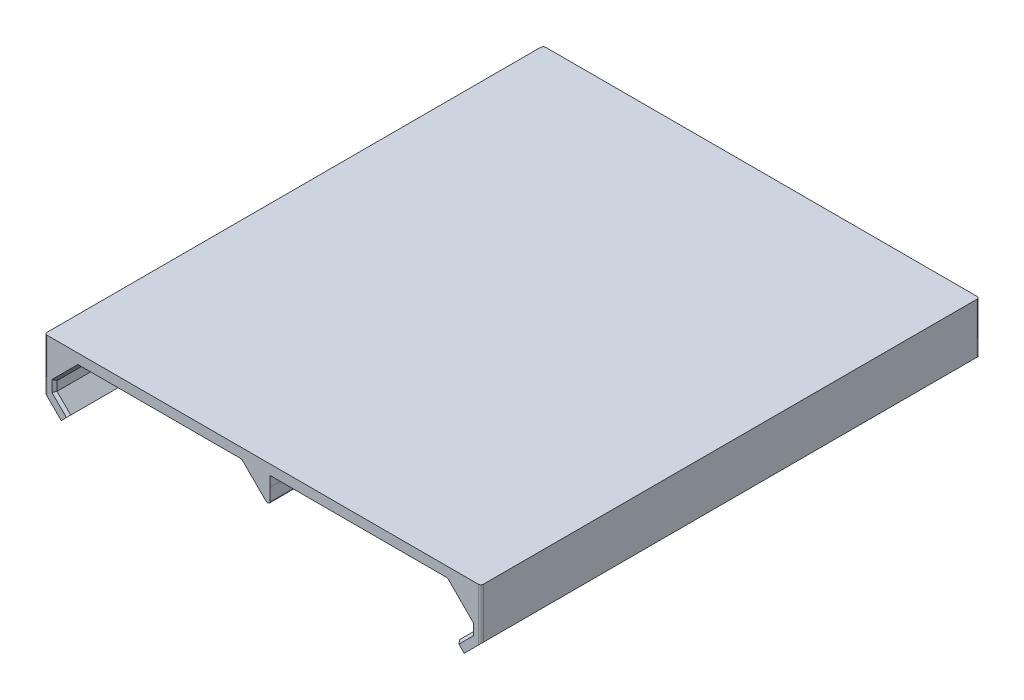
SolidWorks part; units mm, degrees
ref_plane "前视基准面" through (0, 0, 0) normal (0, 0, 1) x (1, 0, 0)
ref_plane "上视基准面" through (0, 0, 0) normal (0, 1, 0) x (1, 0, 0)
ref_plane "右视基准面" through (0, 0, 0) normal (1, 0, 0) x (0, 0, -1)
other "Configuration Table"
sketch "草图1" plane through (0, 0, 0) normal (0, 0, 1) x (1, 0, 0)
  line L0 (0, 0) -> (0, 52) construction
  line L1 (72.7071, 52) -> (-72.7071, 52)
  line L2 (-72.7071, 52) -> (-83.5, 41.2071)
  line L3 (-83.5, 41.2071) -> (-83.5, 37.5)
  line L4 (-83.5, 37.5) -> (-78, 32)
  line L5 (-83, 37) -> (-77, 31) construction
  line L6 (-77, 47) -> (-83, 41) construction
  line L7 (-83, 41) -> (-83, 37) construction
  line L8 (77, 47) -> (74, 47) construction
  line L9 (-77, 31) -> (-77, 0) construction
  line L10 (83.5, 37.5) -> (78, 32)
  line L11 (83.5, 41.2071) -> (83.5, 37.5)
  line L12 (72.7071, 52) -> (83.5, 41.2071)
  line L15 (3.0155, 52) -> (3, 52)
  dimension "D1" = 0.5
  dimension "D2" = 0.5
  dimension "D3" = 5
  dimension "D4" = 1
extrude "拉伸-薄壁1" add sketch "草图1" against normal blind 200 thin thin type one direction reverse wall 4
sketch "草图2" plane through (0, 0, 0) normal (0, 0, 1) x (1, 0, 0)
  line L6 (3, 52) -> (3, 40.5858)
  line L7 (-72.7071, 52) -> (72.7071, 52) construction
  line L8 (3, 40.5858) -> (-8.4142, 52)
  line L9 (-8.4142, 52) -> (3.1511, 52)
  line L10 (3, 20.8) -> (3, 0) construction
  line L13 (-4.8284, 47) -> (3, 39.1716) construction
  line M18 (-72.7071, 52) -> (72.7071, 52)
  dimension "D1" = 1
extrude "凸台-拉伸1" add sketch "草图2" against normal blind 37 contours L8 L6 M18 region at (-0.8047, 48.1953, 0)
other "删除面1" face at (80.932, 49.432, -100) face at (-80.932, 49.432, -100) and patch yes
chamfer "倒角1" distance 1 angle 45 12 edges at (80.75, 34.75, 0) (83.5, 39.3536, 0) (78.1036, 46.6036, 0) (-80.75, 34.75, 0) (-83.5, 39.3536, 0) (-78.1036, 46.6036, 0) (-80.75, 34.75, -200) (-83.5, 39.3536, -200) (-78.1036, 46.6036, -200) (80.75, 34.75, -200) (83.5, 39.3536, -200) (78.1036, 46.6036, -200)
fillet "圆角1" radius 1 5 edges at (-87.5, 45.9216, 0) (-87.5, 45.9216, -200) (87.5, 45.9216, -200) (87.5, 45.9216, 0) (3, 40.5858, -18.5)
